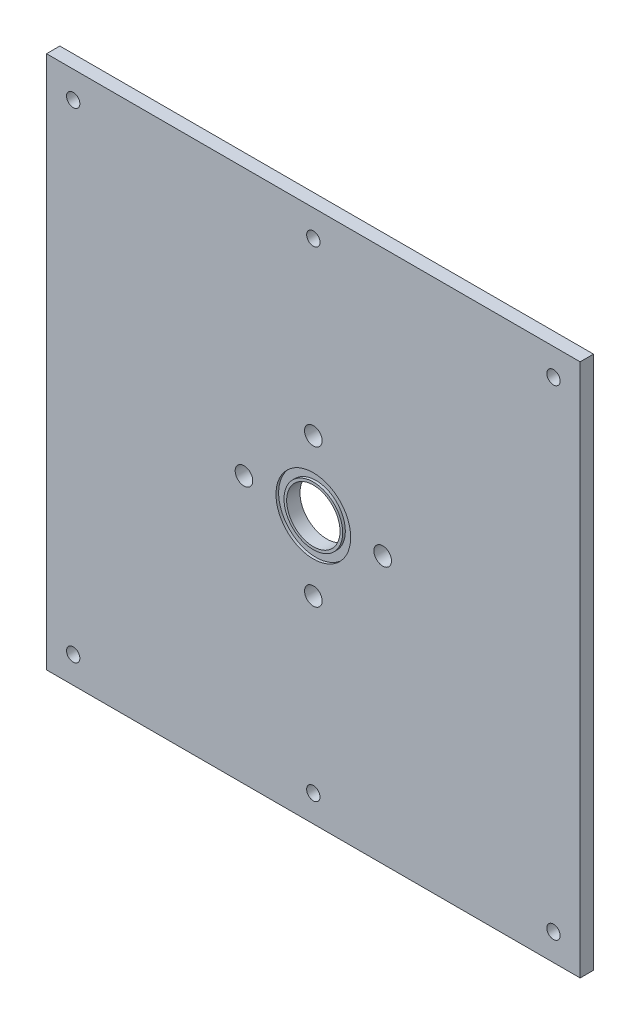
SolidWorks part; units mm, degrees
ref_plane "正面" through (0, 0, 0) normal (0, 0, 1) x (1, 0, 0)
ref_plane "平面" through (0, 0, 0) normal (0, 1, 0) x (1, 0, 0)
ref_plane "右側面" through (0, 0, 0) normal (1, 0, 0) x (0, 0, -1)
sketch "ｽｹｯﾁ1" plane through (0, 0, 0) normal (0, 0, 1) x (1, 0, 0)
  line L1 (-100, 100) -> (100, 100)
  line L2 (-100, 100) -> (-100, -100)
  line L3 (-100, -100) -> (100, -100)
  line L4 (100, 100) -> (100, -100)
  line L5 (-100, 100) -> (100, -100) construction
  line L6 (-100, -100) -> (100, 100) construction
  circle A0 centre (0, 0) radius 10
  point P0 (0, 0)
  dimension "D3" = 20
  dimension "D1" = 200
  dimension "D2" = 200
extrude "ﾎﾞｽ - 押し出し1" add sketch "ｽｹｯﾁ1" along normal blind 5
sketch "ｽｹｯﾁ2" plane through (0, 0, 5) normal (0, 0, 1) x (1, 0, 0)
  circle A0 centre (0, 0) radius 11
  circle A1 centre (0, 0) radius 14
  dimension "D1" = 22
  dimension "D2" = 28
extrude "ｶｯﾄ - 押し出し1" cut sketch "ｽｹｯﾁ2" against normal blind 1
sketch "ｽｹｯﾁ3" plane through (0, 0, 5) normal (0, 0, 1) x (1, 0, 0)
  line L0 (100, 100) -> (-100, 100) construction
  line L1 (-90, 90) -> (90, 90) construction
  line L2 (-90, 90) -> (-90, -90) construction
  line L3 (-90, -90) -> (90, -90) construction
  line L4 (90, 90) -> (90, -90) construction
  line L5 (-90, 90) -> (90, -90) construction
  line L6 (-90, -90) -> (90, 90) construction
  line L7 (-100, 100) -> (-100, -100) construction
  circle A0 centre (0, 90) radius 2.5
  circle A1 centre (90, 90) radius 2.5
  circle A2 centre (-90, 90) radius 2.5
  circle A3 centre (-90, -90) radius 2.5
  circle A4 centre (0, -90) radius 2.5
  circle A5 centre (90, -90) radius 2.5
  point P0 (0, 0)
  dimension "D3" = 5
  dimension "D1" = 10
  dimension "D2" = 10
extrude "ｶｯﾄ - 押し出し2" cut sketch "ｽｹｯﾁ3" against normal through all
sketch "ｽｹｯﾁ5" plane through (0, 0, 0) normal (0, 0, -1) x (-1, 0, 0)
  circle A0 centre (-26, 0) radius 3.3 construction
  circle A1 centre (0, -26) radius 3.3 construction
  circle A2 centre (26, 0) radius 3.3 construction
  circle A3 centre (0, 26) radius 3.3 construction
  circle A4 centre (-26, 0) radius 3.3
  circle A5 centre (0, -26) radius 3.3
  circle A6 centre (26, 0) radius 3.3
  circle A7 centre (0, 26) radius 3.3
extrude "ｶｯﾄ - 押し出し4" cut sketch "ｽｹｯﾁ5" against normal through all
